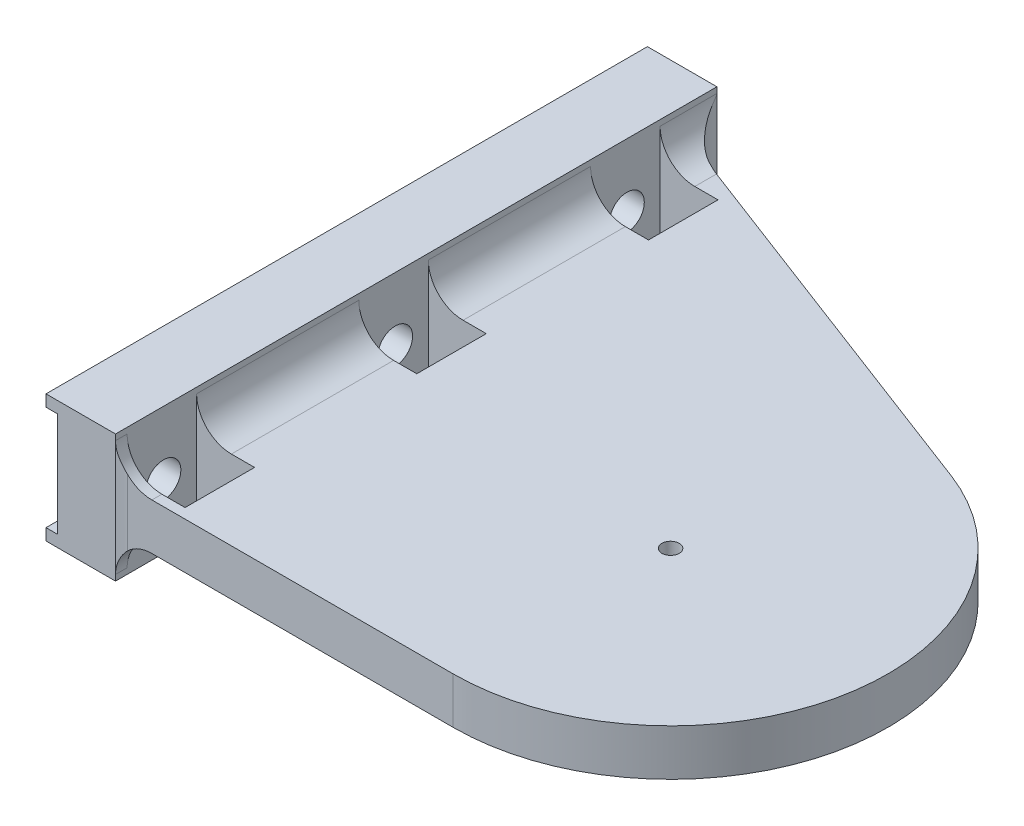
SolidWorks part; units mm, degrees
ref_plane "前视基准面" through (0, 0, 0) normal (0, 0, 1) x (1, 0, 0)
ref_plane "上视基准面" through (0, 0, 0) normal (0, 1, 0) x (1, 0, 0)
ref_plane "右视基准面" through (0, 0, 0) normal (1, 0, 0) x (0, 0, -1)
ref_plane "基准面4" through (0, 0, 0) normal (0, -1, 0) x (1, 0, 0)
sketch "草图1" plane through (0, 0, 0) normal (0, -1, 0) x (1, 0, 0)
  line L0 (-29, 18.9063) -> (-29, -33)
  line L1 (-27.0707, -30.3664) -> (6.6677, -17.5436)
  line L2 (0, 18.768) -> (-28.0994, 18.768)
  arc A0 (-28.0994, 18.768) -> (-29, 18.9063) centre (-28.0994, 21.768) cw
  arc A1 (-29, -33) -> (-27.0707, -30.3664) centre (-26.0049, -33.1707) cw
  arc A2 (6.6677, -17.5436) -> (0, 18.768) centre (0, 0) ccw
extrude "凸台-拉伸1" add sketch "草图1" against normal blind 4
sketch "草图2" plane through (0, 4, 0) normal (0, 1, 0) x (-1, 0, 0)
  line L0 (29, 18.768) -> (29, -20.0778)
  line L1 (29, -20.0778) -> (0, -20.0778)
  line L2 (0, -20.0778) -> (0, 18.768)
  line L3 (0, 18.768) -> (29, 18.768)
extrude "凸台-拉伸2" add sketch "草图2" along normal blind 3.5
sketch "草图3" plane through (0, 0, 18.768) normal (0, 0, 1) x (1, 0, 0)
  line L0 (-29, 4) -> (-29, 7.5)
  line L1 (-29, 7.5) -> (0, 7.5)
  line L2 (0, 7.5) -> (0, 4)
  line L3 (0, 4) -> (-29, 4)
extrude "凸台-拉伸3" add sketch "草图3" along normal blind 0.1384
sketch "草图4" plane through (0, 0, -20.0778) normal (0, 0, -1) x (-1, 0, 0)
  line L0 (29, 7.5) -> (29, 4)
  line L1 (29, 4) -> (0, 4)
  line L2 (0, 4) -> (0, 7.5)
  line L3 (0, 7.5) -> (29, 7.5)
extrude "凸台-拉伸4" add sketch "草图4" along normal blind 12.9222
sketch "草图5" plane through (-29, 0, 0) normal (-1, 0, 0) x (0, 0, 1)
  line L0 (18.9063, 0) -> (-33, 0)
  line L1 (-33, 0) -> (-33, 7.5)
  line L2 (-33, 7.5) -> (18.9063, 7.5)
  line L3 (18.9063, 7.5) -> (18.9063, 0)
extrude "凸台-拉伸5" add sketch "草图5" along normal blind 6
sketch "草图6" plane through (0, 0, 0) normal (1, 0, 0) x (0, 0, -1)
  line L0 (-18.9063, 4) -> (-18.768, 4)
  line L1 (-18.768, 4) -> (31.0229, 4)
  line L2 (31.0229, 4) -> (33, 4)
  line L3 (33, 4) -> (33, 7.5)
  line L4 (33, 7.5) -> (-18.9063, 7.5)
  line L5 (-18.9063, 7.5) -> (-18.9063, 4)
extrude "切除-拉伸1" cut sketch "草图6" against normal blind 28.0994
sketch "草图7" plane through (-28.0994, 0, 0) normal (1, 0, 0) x (0, 0, -1)
  line L0 (-18.9063, 4) -> (33, 4)
  line L1 (33, 4) -> (33, 7.5)
  line L2 (33, 7.5) -> (-18.9063, 7.5)
  line L3 (-18.9063, 7.5) -> (-18.9063, 4)
extrude "切除-拉伸2" cut sketch "草图7" against normal blind 0.9006
ref_plane "基准面5" through (0, 0, -28.0937) normal (0, 0, -1) x (-1, 0, 0)
sketch "草图8" plane through (0, 0, -28.0937) normal (0, 0, -1) x (-1, 0, 0)
  line L0 (24, 0) -> (29, 0)
  line L1 (29, 0) -> (29, 4)
  line L2 (29, 4) -> (24, 4)
  line L3 (24, 4) -> (24, 0)
extrude "切除-拉伸3" cut sketch "草图8" against normal blind 6
ref_plane "基准面6" through (0, 0, 17.9063) normal (0, 0, 1) x (1, 0, 0)
sketch "草图9" plane through (0, 0, 17.9063) normal (0, 0, 1) x (1, 0, 0)
  line L0 (-29, 4) -> (-29, 0)
  line L1 (-29, 0) -> (-24, 0)
  line L2 (-24, 0) -> (-24, 4)
  line L3 (-24, 4) -> (-29, 4)
extrude "切除-拉伸4" cut sketch "草图9" against normal blind 6
ref_plane "基准面7" through (0, 0, -2.0937) normal (0, 0, 1) x (1, 0, 0)
sketch "草图10" plane through (0, 0, -2.0937) normal (0, 0, 1) x (1, 0, 0)
  line L0 (-29, 4) -> (-29, 0)
  line L1 (-29, 0) -> (-24, 0)
  line L2 (-24, 0) -> (-24, 4)
  line L3 (-24, 4) -> (-29, 4)
extrude "切除-拉伸5" cut sketch "草图10" against normal blind 6
sketch "草图11" plane through (0, 0, 0) normal (0, -1, 0) x (1, 0, 0)
  line L0 (-29, -33) -> (-35, -33)
  line L1 (-35, -33) -> (-35, 18.9063)
  line L2 (-35, 18.9063) -> (-29, 18.9063)
  line L3 (-29, 18.9063) -> (-29, -33)
extrude "凸台-拉伸6" add sketch "草图11" along normal blind 3.5
sketch "草图12" plane through (0, 0, 18.9063) normal (0, 0, 1) x (1, 0, 0)
  line L0 (-35, 6.5) -> (-35, -2.5)
  line L1 (-35, -2.5) -> (-34, -2.5)
  line L2 (-34, -2.5) -> (-34, 6.5)
  line L3 (-34, 6.5) -> (-35, 6.5)
extrude "切除-拉伸6" cut sketch "草图12" against normal through all
hole_wizard "Ø3.0 (3) 直径孔1" positions "草图14" profile "草图13" hole size "Ø3.0" standard "ANSI Metric"
sketch "草图14" plane through (-29, 0, 0) normal (1, 0, 0) x (0, 0, -1)
  point P0 (25.232, 2)
sketch "草图13" plane through (-29, 2, -25.232) normal (0, 1, 0) x (0, 0, -1)
  line L0 (0, 0) -> (0, 6)
  line L1 (0, 6) -> (1.5, 6)
  line L2 (1.5, 6) -> (1.5, 0)
  line L5 (1.5, 0) -> (0, 0)
  line L11 (0, -6.35) -> (0, 107.95) construction
  dimension "通孔孔直径" = 3
  dimension "通孔孔深度" = 6
hole_wizard "Ø3.0 (3) 直径孔2" positions "草图16" profile "草图15" hole size "Ø3.0" standard "ANSI Metric"
sketch "草图16" plane through (-34, 0, 0) normal (-1, 0, 0) x (0, 0, 1)
  point P0 (14.768, 2)
  point P1 (-5.232, 2)
sketch "草图15" plane through (-34, 2, 14.768) normal (0, 1, 0) x (0, 0, 1)
  line L0 (0, 0) -> (0, 5)
  line L1 (0, 5) -> (1.5, 5)
  line L2 (1.5, 5) -> (1.5, 0)
  line L5 (1.5, 0) -> (0, 0)
  line L11 (0, -6.35) -> (0, 107.95) construction
  dimension "通孔孔直径" = 3
  dimension "通孔孔深度" = 5
hole_wizard "Ø8.0 (8) 直径孔1" positions "草图18" profile "草图17" hole size "Ø8.0" standard "ANSI Metric"
sketch "草图18" plane through (0, 0, 0) normal (0, -1, 0) x (-1, 0, 0)
  point P0 (0, 0)
sketch "草图17" plane through (0, 0, 0) normal (1, 0, 0) x (0, 0, -1)
  line L0 (0, 0) -> (0, 7.5)
  line L1 (0, 7.5) -> (0.75, 7.5)
  line L2 (0.75, 7.5) -> (0.75, 0)
  line L5 (0.75, 0) -> (0, 0)
  line L11 (0, -6.35) -> (0, 107.95) construction
  dimension "通孔孔直径" = 1.5
  dimension "通孔孔深度" = 7.5
fillet "圆角1" radius 3 8 edges tangent propagation no
sketch "草图21" plane through (0, 4, 0) normal (0, 1, 0) x (1, 0, 0)
